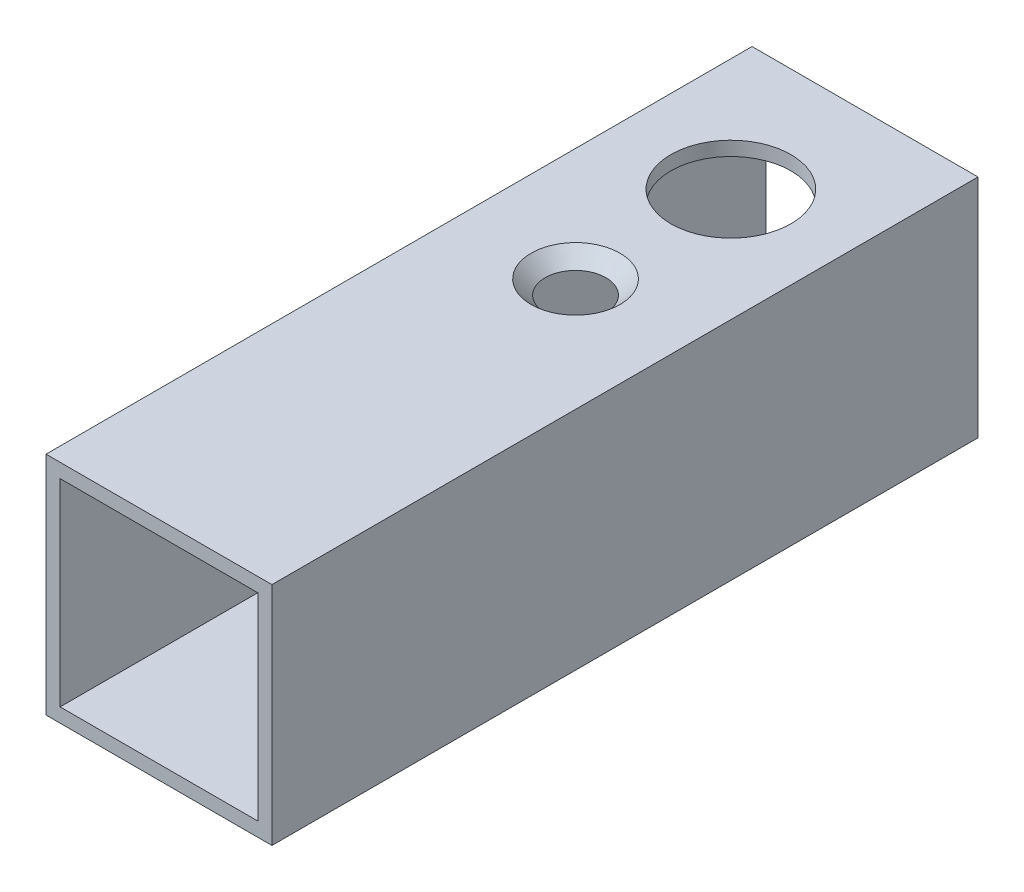
SolidWorks part; units mm, degrees
ref_plane "Front Plane" through (0, 0, 0) normal (0, 0, 1) x (1, 0, 0)
ref_plane "Top Plane" through (0, 0, 0) normal (0, 1, 0) x (1, 0, 0)
ref_plane "Right Plane" through (0, 0, 0) normal (1, 0, 0) x (0, 0, -1)
sketch "Sketch1" plane through (0, 0, 0) normal (0, 0, 1) x (1, 0, 0)
  line L1 (-7, -7) -> (7, -7)
  line L2 (-7, -7) -> (-7, 7)
  line L3 (-7, 7) -> (7, 7)
  line L4 (7, -7) -> (7, 7)
  line L5 (-7, -7) -> (7, 7) construction
  line L6 (-7, 7) -> (7, -7) construction
  line L7 (-8, -8) -> (8, -8)
  line L8 (-8, -8) -> (-8, 8)
  line L9 (-8, 8) -> (8, 8)
  line L10 (8, -8) -> (8, 8)
  line L11 (-8, -8) -> (8, 8) construction
  line L12 (-8, 8) -> (8, -8) construction
  point P0 (0, 0)
  point P6 (0, 0)
  dimension "D1" = 16
  dimension "D2" = 1
extrude "Boss-Extrude1" add sketch "Sketch1" along normal blind 50
ref_axis "Axis1" through (0, 0, -15) along (0, 0, 1)
sketch "Sketch2" plane through (0, 8, 0) normal (0, 1, 0) x (1, 0, 0)
  circle A0 centre (0, -9.5) radius 4.25
  dimension "D1" = 8.5
extrude "Cut-Extrude1" cut sketch "Sketch2" against normal through all
sketch "Sketch3" plane through (0, 8, 0) normal (0, 1, 0) x (1, 0, 0)
  circle A0 centre (0, -20.5) radius 1.4 construction
  circle A1 centre (0, -20.5) radius 1.4
hole_wizard "CSK for M3 Flat Head Machine Screw1" positions "3DSketch1" profile "Sketch4" countersink size "M3" standard "ANSI Metric" end condition through all
sketch3d "3DSketch1"
  point P0 (0, 8, 20.5)
sketch "Sketch4" plane through (0, 8, 20.5) normal (1, 0, 0) x (0, 0, 1)
  line L0 (0, 0) -> (0, 16)
  line L1 (0, 16) -> (1.7, 16)
  line L2 (1.7, 16) -> (1.7, 1.45)
  line L3 (1.7, 1.45) -> (3.15, 0)
  line L5 (3.15, 0) -> (0, 0)
  line L6 (-1.7, 1.45) -> (-3.15, 0) construction
  line L11 (0, -6.35) -> (0, 107.95) construction
  dimension "Thru Hole Dia." = 3.4
  dimension "Thru Hole Depth" = 16
  dimension "Near C'Sink Dia." = 6.3
  dimension "Near C'Sink Angle" = 90
mirror "Mirror1" about plane through (0, 0, 0) normal (0, 1, 0) of "CSK for M3 Flat Head Machine Screw1"
